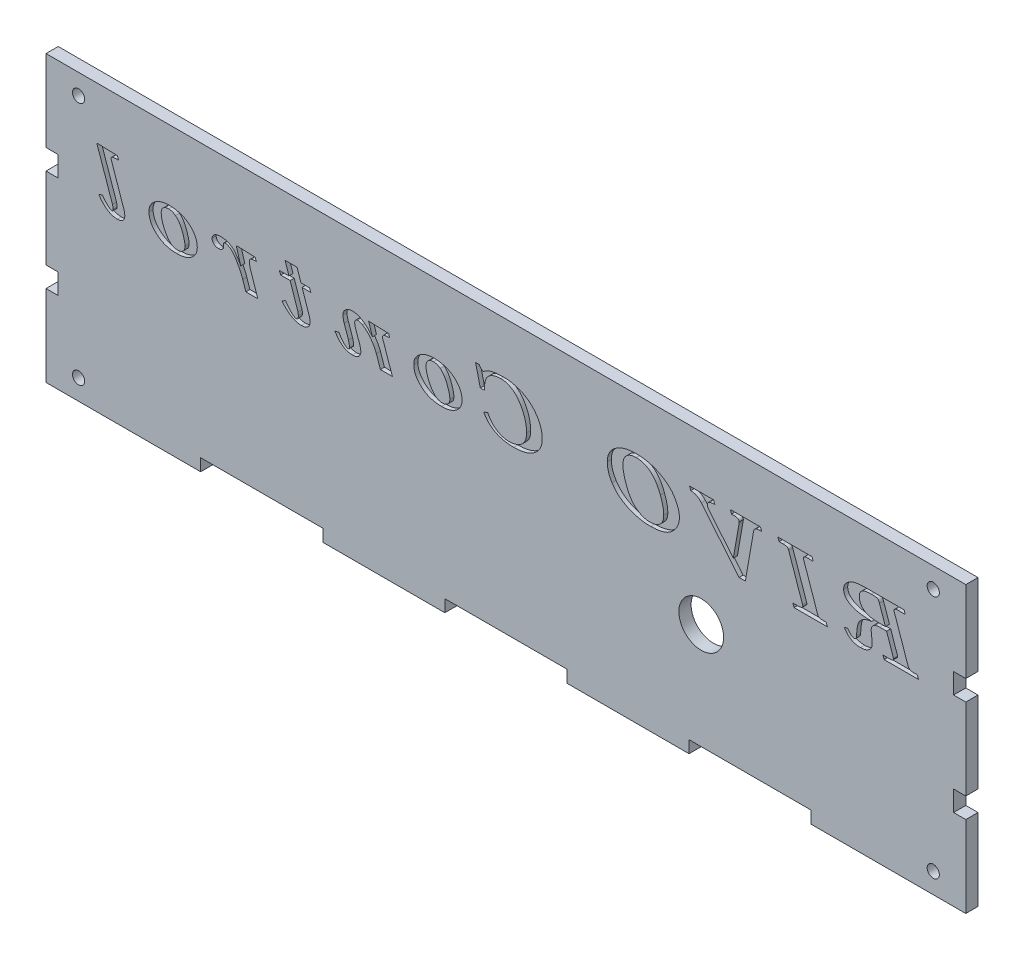
SolidWorks part; units mm, degrees
ref_plane "Front Plane" through (0, 0, 0) normal (0, 0, 1) x (1, 0, 0)
ref_plane "Top Plane" through (0, 0, 0) normal (0, 1, 0) x (1, 0, 0)
ref_plane "Right Plane" through (0, 0, 0) normal (1, 0, 0) x (0, 0, -1)
sketch "Sketch1" plane through (0, 0, 0) normal (0, 0, 1) x (1, 0, 0)
  line L1 (0, 0) -> (220, 0)
  line L2 (0, 0) -> (0, 70)
  line L3 (0, 70) -> (220, 70)
  line L4 (220, 0) -> (220, 70)
  dimension "D1" = 220
  dimension "D2" = 70
extrude "Boss-Extrude1" add sketch "Sketch1" along normal blind 3
sketch "Sketch2" plane through (0, 0, 3) normal (0, 0, 1) x (1, 0, 0)
  line L0 (110, 70) -> (110, 0) construction
  line L1 (220, 70) -> (0, 70) construction
  line L2 (0, 0) -> (220, 0) construction
  line L4 (0, 44) -> (220, 44) construction
  line L5 (5, 5) -> (215, 5) construction
  line L6 (5, 5) -> (5, 65) construction
  line L7 (5, 65) -> (215, 65) construction
  line L8 (215, 5) -> (215, 65) construction
  line L9 (5, 5) -> (215, 65) construction
  line L10 (5, 65) -> (215, 5) construction
  circle A0 centre (5, 65) radius 1.5
  circle A1 centre (215, 65) radius 1.5
  circle A2 centre (215, 5) radius 1.5
  circle A3 centre (5, 5) radius 1.5
  text T0 "RIVO Control" font "Century Schoolbook" height in points 50
  point P9 (110, 44)
  point P10 (110, 35)
  dimension "D5" = 3
  dimension "D1" = 220
  dimension "D2" = 26
  dimension "D3" = 210
  dimension "D4" = 60
extrude "Cut-Extrude1" cut sketch "Sketch2" against normal blind 1
extrude "Cut-Extrude2" cut sketch "Sketch2<2>" against normal through all contours A0 | A3 | A2 | A1 region at (5, 65, 3) region at (215, 65, 3) region at (215, 5, 3) region at (5, 5, 3)
sketch "Sketch2<2>" plane through (0, 0, 3) normal (0, 0, 1) x (1, 0, 0) same geometry as "Sketch2"
sketch "Sketch3" plane through (0, 0, 3) normal (0, 0, 1) x (1, 0, 0)
  line L0 (0, 35) -> (220, 35) construction
  line L1 (0, 70) -> (0, 0) construction
  line L2 (220, 0) -> (220, 70) construction
  line L3 (-3, 45) -> (0, 25) construction
  line L4 (0, 25) -> (-3, 25)
  line L5 (0, 25) -> (0, 45)
  line L6 (0, 45) -> (-3, 45)
  line L7 (-3, 25) -> (-3, 45)
  line L8 (0, 45) -> (-3, 25) construction
  line L9 (0, 35) -> (-3, 35) construction
  line L10 (-3, 70) -> (0, 50) construction
  line L11 (0, 70) -> (-3, 50) construction
  line L12 (0, 70) -> (-3, 70)
  line L13 (-3, 50) -> (-3, 70)
  line L14 (0, 60) -> (-3, 60) construction
  line L15 (0, 50) -> (-3, 50)
  line L16 (-3, 20) -> (0, 0) construction
  line L17 (0, 20) -> (-3, 0) construction
  line L18 (0, 20) -> (-3, 20)
  line L19 (-3, 0) -> (-3, 20)
  line L20 (0, 10) -> (-3, 10) construction
  line L21 (0, 0) -> (-3, 0)
  line L22 (110, 0) -> (110, 70) construction
  line L23 (0, 0) -> (220, 0) construction
  line L24 (220, 70) -> (0, 70) construction
  line L25 (220, 10) -> (223, 10) construction
  line L26 (220, 20) -> (223, 0) construction
  line L27 (223, 20) -> (220, 0) construction
  line L28 (220, 60) -> (223, 60) construction
  line L29 (220, 70) -> (223, 50) construction
  line L30 (223, 70) -> (220, 50) construction
  line L31 (220, 35) -> (223, 35) construction
  line L32 (220, 45) -> (223, 25) construction
  line L33 (223, 45) -> (220, 25) construction
  line L34 (220, 0) -> (223, 0)
  line L35 (223, 0) -> (223, 20)
  line L36 (220, 20) -> (223, 20)
  line L37 (220, 50) -> (223, 50)
  line L38 (223, 50) -> (223, 70)
  line L39 (220, 70) -> (223, 70)
  line L40 (223, 25) -> (223, 45)
  line L41 (220, 45) -> (223, 45)
  line L42 (220, 25) -> (220, 45)
  line L43 (220, 25) -> (223, 25)
  line L44 (0, 70) -> (0, 0)
  line L45 (220, 0) -> (220, 70)
  point P10 (-1.5, 35)
  dimension "D1" = 20
  dimension "D2" = 3
  dimension "D3" = 2
  dimension "D4" = 2
extrude "Boss-Extrude4" add sketch "Sketch3" against normal up to surface (3 mm away) contours L7 L4 L5 L6 | L42 L43 L40 L41 region at (-1.5, 35, 3) region at (221.5, 35, 3) up to face at (216.5, 65, 0)
pattern_linear "LPattern1" count 2 spacing 25 along (0, 1, 0) count 2 spacing 25 along (0, -1, 0) of "Boss-Extrude4"
sketch "Sketch4" plane through (0, 0, 0) normal (0, 0, -1) x (-1, 0, 0)
  line L0 (-155, 0) -> (-185, 0) construction
  line L1 (-185, 0) -> (-185, 3) construction
  line L2 (-185, 3) -> (-155, 3) construction
  line L3 (-155, 3) -> (-155, 0) construction
  line L4 (-95, 0) -> (-125, 0) construction
  line L5 (-125, 0) -> (-125, 3) construction
  line L6 (-125, 3) -> (-95, 3) construction
  line L7 (-95, 3) -> (-95, 0) construction
  line L8 (-35, 0) -> (-65, 0) construction
  line L9 (-65, 0) -> (-65, 3) construction
  line L10 (-65, 3) -> (-35, 3) construction
  line L11 (-35, 3) -> (-35, 0) construction
  line L12 (-155, 0) -> (-185, 0)
  line L13 (-185, 0) -> (-185, 3)
  line L14 (-185, 3) -> (-155, 3)
  line L15 (-155, 3) -> (-155, 0)
  line L16 (-95, 0) -> (-125, 0)
  line L17 (-125, 0) -> (-125, 3)
  line L18 (-125, 3) -> (-95, 3)
  line L19 (-95, 3) -> (-95, 0)
  line L20 (-35, 0) -> (-65, 0)
  line L21 (-65, 0) -> (-65, 3)
  line L22 (-65, 3) -> (-35, 3)
  line L23 (-35, 3) -> (-35, 0)
extrude "Cut-Extrude3" cut sketch "Sketch4" against normal through all
sketch "Sketch5" plane through (0, 0, 3) normal (0, 0, 1) x (1, 0, 0)
  line L0 (158, 43.0279) -> (158, 3) construction
  line L2 (155, 3) -> (185, 3) construction
  line L3 (223, 0) -> (223, 20) construction
  circle A0 centre (158, 29) radius 5.5
  dimension "D1" = 11
  dimension "D2" = 26
  dimension "D3" = 65
extrude "Cut-Extrude4" cut sketch "Sketch5" against normal through all
sketch "Sketch6" plane through (0, 0, 0) normal (0, 0, -1) x (-1, 0, 0)
  line L0 (-140, 0) -> (-140, 70) construction
  line L1 (-125, 0) -> (-155, 0) construction
  line L2 (-223, 70) -> (3, 70) construction
  line L3 (-146.5, 50.5) -> (-133.5, 45.5) construction
  line L4 (-146.5, 45.5) -> (-133.5, 45.5)
  line L5 (-146.5, 45.5) -> (-146.5, 50.5)
  line L6 (-146.5, 50.5) -> (-133.5, 50.5)
  line L7 (-133.5, 45.5) -> (-133.5, 50.5)
  line L8 (-133.5, 50.5) -> (-146.5, 45.5) construction
  line L9 (-196.5, 45.5) -> (-196.5, 50.5)
  line L10 (-196.5, 45.5) -> (-183.5, 45.5)
  line L11 (-183.5, 45.5) -> (-183.5, 50.5)
  line L12 (-196.5, 50.5) -> (-183.5, 50.5)
  line L13 (-196.5, 35.5) -> (-196.5, 40.5)
  line L14 (-196.5, 35.5) -> (-183.5, 35.5)
  line L15 (-183.5, 35.5) -> (-183.5, 40.5)
  line L16 (-196.5, 40.5) -> (-183.5, 40.5)
  line L17 (-196.5, 25.5) -> (-196.5, 30.5)
  line L18 (-196.5, 25.5) -> (-183.5, 25.5)
  line L19 (-183.5, 25.5) -> (-183.5, 30.5)
  line L20 (-196.5, 30.5) -> (-183.5, 30.5)
  line L21 (-196.5, 15.5) -> (-196.5, 20.5)
  line L22 (-196.5, 15.5) -> (-183.5, 15.5)
  line L23 (-183.5, 15.5) -> (-183.5, 20.5)
  line L24 (-196.5, 20.5) -> (-183.5, 20.5)
  line L25 (-146.5, 35.5) -> (-146.5, 40.5)
  line L26 (-146.5, 35.5) -> (-133.5, 35.5)
  line L27 (-133.5, 35.5) -> (-133.5, 40.5)
  line L28 (-146.5, 40.5) -> (-133.5, 40.5)
  line L29 (-146.5, 25.5) -> (-146.5, 30.5)
  line L30 (-146.5, 25.5) -> (-133.5, 25.5)
  line L31 (-133.5, 25.5) -> (-133.5, 30.5)
  line L32 (-146.5, 30.5) -> (-133.5, 30.5)
  line L33 (-146.5, 15.5) -> (-146.5, 20.5)
  line L34 (-146.5, 15.5) -> (-133.5, 15.5)
  line L35 (-133.5, 15.5) -> (-133.5, 20.5)
  line L36 (-146.5, 20.5) -> (-133.5, 20.5)
  line L37 (-110, 70) -> (-110, 3) construction
  line L38 (-95, 3) -> (-125, 3) construction
  line L39 (-86.5, 50.5) -> (-73.5, 45.5) construction
  line L40 (-73.5, 50.5) -> (-86.5, 45.5) construction
  line L41 (-80, 0) -> (-80, 70) construction
  line L42 (-73.5, 20.5) -> (-86.5, 20.5)
  line L43 (-86.5, 15.5) -> (-86.5, 20.5)
  line L44 (-73.5, 15.5) -> (-86.5, 15.5)
  line L45 (-73.5, 15.5) -> (-73.5, 20.5)
  line L46 (-73.5, 30.5) -> (-86.5, 30.5)
  line L47 (-86.5, 25.5) -> (-86.5, 30.5)
  line L48 (-73.5, 25.5) -> (-86.5, 25.5)
  line L49 (-73.5, 25.5) -> (-73.5, 30.5)
  line L50 (-73.5, 40.5) -> (-86.5, 40.5)
  line L51 (-86.5, 35.5) -> (-86.5, 40.5)
  line L52 (-73.5, 35.5) -> (-86.5, 35.5)
  line L53 (-73.5, 35.5) -> (-73.5, 40.5)
  line L54 (-23.5, 20.5) -> (-36.5, 20.5)
  line L55 (-36.5, 15.5) -> (-36.5, 20.5)
  line L56 (-23.5, 15.5) -> (-36.5, 15.5)
  line L57 (-23.5, 15.5) -> (-23.5, 20.5)
  line L58 (-23.5, 30.5) -> (-36.5, 30.5)
  line L59 (-36.5, 25.5) -> (-36.5, 30.5)
  line L60 (-23.5, 25.5) -> (-36.5, 25.5)
  line L61 (-23.5, 25.5) -> (-23.5, 30.5)
  line L62 (-23.5, 40.5) -> (-36.5, 40.5)
  line L63 (-36.5, 35.5) -> (-36.5, 40.5)
  line L64 (-23.5, 35.5) -> (-36.5, 35.5)
  line L65 (-23.5, 35.5) -> (-23.5, 40.5)
  line L66 (-23.5, 50.5) -> (-36.5, 50.5)
  line L67 (-36.5, 45.5) -> (-36.5, 50.5)
  line L68 (-23.5, 45.5) -> (-36.5, 45.5)
  line L69 (-23.5, 45.5) -> (-23.5, 50.5)
  line L70 (-86.5, 45.5) -> (-86.5, 50.5)
  line L71 (-73.5, 50.5) -> (-86.5, 50.5)
  line L72 (-73.5, 45.5) -> (-73.5, 50.5)
  line L73 (-73.5, 45.5) -> (-86.5, 45.5)
  point P6 (-140, 48)
  point P12 (-140, 48)
  point P78 (-80, 48)
  dimension "D1" = 13
  dimension "D2" = 5
  dimension "D3" = 22
  dimension "D4" = 2
  dimension "D5" = 4
extrude "Cut-Extrude5" [suppressed] cut sketch "Sketch6" against normal through all
